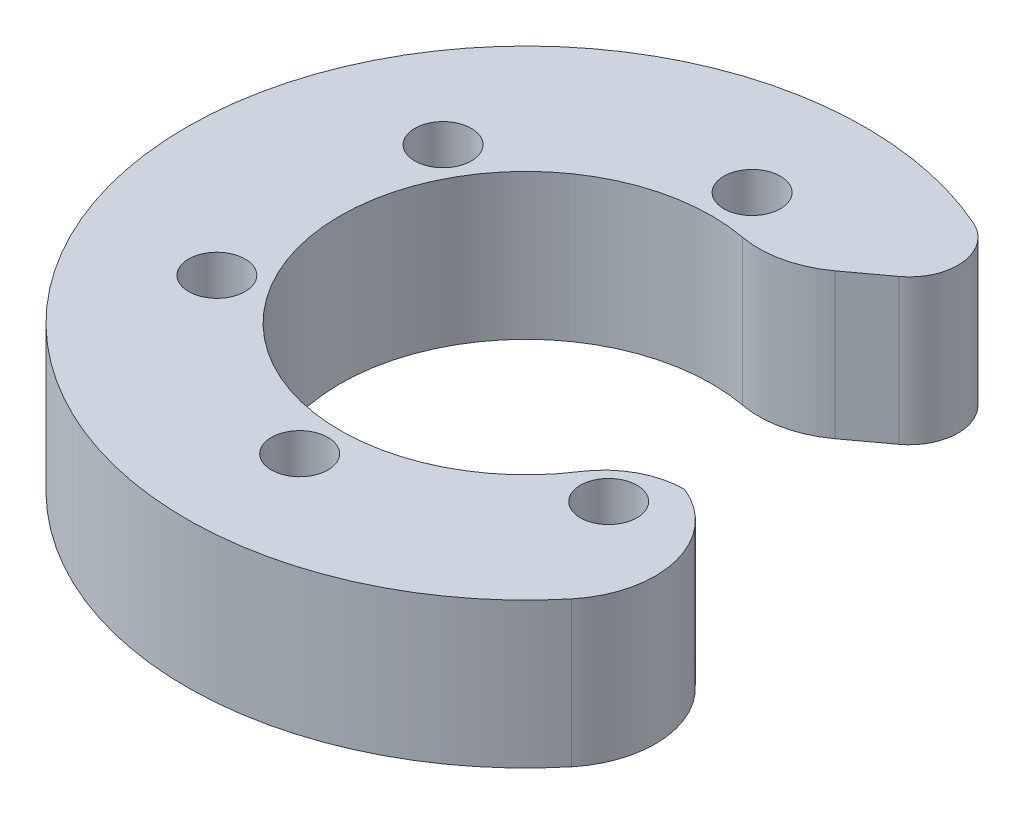
SolidWorks part; units mm, degrees
note: '?' marks a value the reader was unsure of.
material "黄铜"
ref_plane "前视基准面" through (0, 0, 0) normal (0, 0, 1) x (1, 0, 0)
ref_plane "上视基准面" through (0, 0, 0) normal (0, 1, 0) x (1, 0, 0)
ref_plane "右视基准面" through (0, 0, 0) normal (1, 0, 0) x (0, 0, -1)
sketch "草图1" plane through (0, 0, 0) normal (0, 1, 0) x (1, 0, 0)
  circle A0 centre (0, 0) radius 21
  dimension "D1" = 42
extrude "凸台-拉伸1" add sketch "草图1" along normal blind 9
sketch "草图2" plane through (0, 9, 0) normal (0, 1, 0) x (1, 0, 0)
  circle A0 centre (0, 0) radius 14
  dimension "D1" = 28
sketch "草图3" plane through (0, 9, 0) normal (0, 1, 0) x (1, 0, 0)
  circle A0 centre (0, 0) radius 14 construction
  point P0 (0, 14)
hole_wizard "孔1" positions "草图3" profile "草图4" legacy end condition up to next
sketch "草图4" plane through (0, 9, -14) normal (1, 0, 0) x (0, 0, 1)
  line L0 (0, 0) -> (0, 9)
  line L1 (0, 9) -> (1.75, 9)
  line L2 (1.75, 9) -> (1.75, 0)
  line L3 (1.75, 0) -> (0, 0)
  line L4 (0, 110) -> (0, -10) construction
  dimension "直径" = 3.5
  dimension "深度" = 9
ref_axis "基准轴1" through (0, 0, 0) along (0, 1, 0)?
pattern_circular "阵列(圆周)1" count 6 every 60 about axis through (0, 0, 0) along (0, 1, 0) of "孔1"
sketch "草图5" plane through (0, 9, 0) normal (0, 1, 0) x (1, 0, 0)
  point P0 (0, 0)
hole_wizard "孔2" positions "草图5" profile "草图6" legacy end condition up to next
sketch "草图6" plane through (0, 9, 0) normal (1, 0, 0) x (0, 0, 1)
  line L0 (0, 0) -> (0, 9)
  line L1 (0, 9) -> (11.5, 9)
  line L2 (11.5, 9) -> (11.5, 0)
  line L3 (11.5, 0) -> (0, 0)
  line L4 (0, 110) -> (0, -10) construction
  dimension "直径" = 23
  dimension "深度" = 9
sketch "草图7" plane through (0, 0, 0) normal (0, -1, 0) x (1, 0, 0)
  line L0 (0, 0) -> (14, 0)
  line L1 (4, -4) -> (24, -4)
  line L2 (4, -4) -> (4, 4)
  line L3 (4, 4) -> (24, 4)
  line L4 (24, -4) -> (24, 4)
  line L5 (4, -4) -> (24, 4) construction
  line L6 (4, 4) -> (24, -4) construction
  circle A0 centre (0, 0) radius 14 construction
  point P0 (14, 0)
  dimension "D1" = 8
  dimension "D2" = 20
extrude "切除-拉伸1" cut sketch "草图7" against normal blind 10
fillet "圆角1" radius 5 2 edges at (10.7819, 4.5, 4) (10.7819, 4.5, -4)
fillet "圆角2" radius 6 2 edges at (20.6155, 4.5, 4) (20.6155, 4.5, -4)
sketch "草图8" plane through (0, 0, 0) normal (0, -1, 0) x (-1, 0, 0)
  line L0 (1.2574, 6.4551) -> (-16.6074, 19.6203)
  line L1 (1.2574, 6.4551) -> (-7.6413, -5.6203)
  line L2 (-16.6074, 19.6203) -> (-25.5061, 7.5449)
  line L3 (-7.6413, -5.6203) -> (-25.5061, 7.5449)
  line L4 (1.2574, 6.4551) -> (-25.5061, 7.5449) construction
  line L5 (-16.6074, 19.6203) -> (-7.6413, -5.6203) construction
  circle A0 centre (0, 0) radius 14 construction
  point P0 (-12.1244, 7)
  point P1 (-12.1244, 7)
  dimension "D1" = 15
extrude "切除-拉伸2" cut sketch "草图8" against normal blind 10
fillet "圆角3" radius 6 1 edges at (4.4007, 4.5, -10.6247)
fillet "圆角4" radius 3 1 edges at (12.6892, 4.5, -16.7328)
